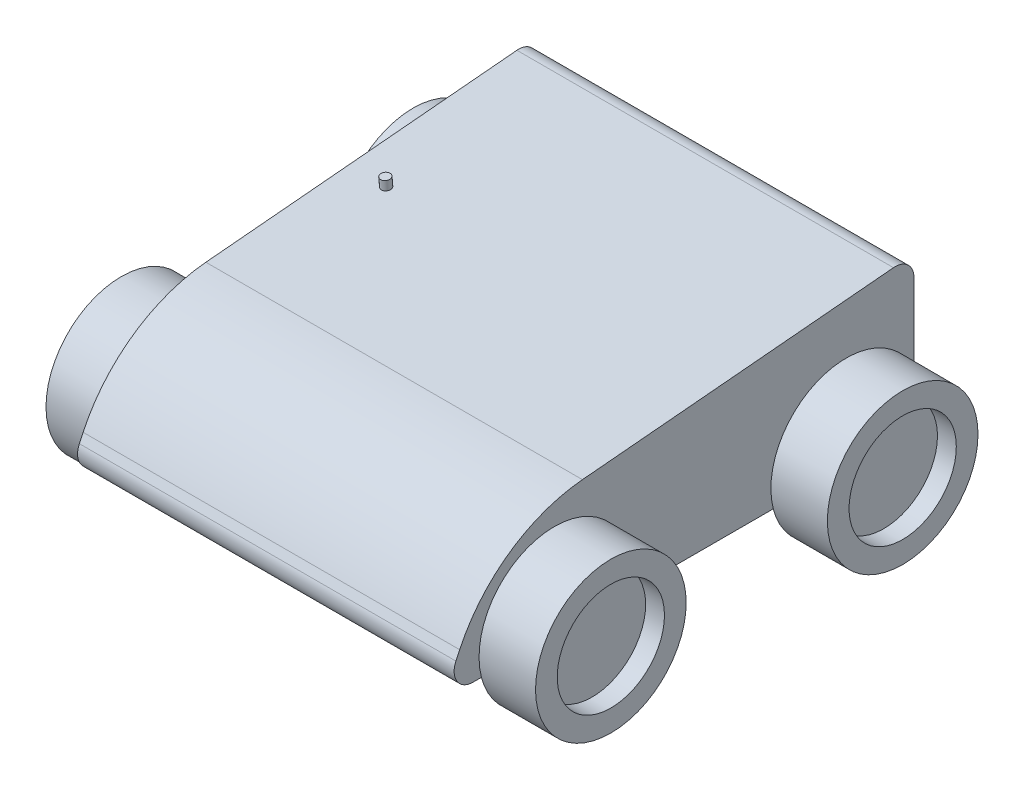
SolidWorks part; units mm, degrees
ref_plane "Front Plane" through (0, 0, 0) normal (0, 0, 1) x (1, 0, 0)
ref_plane "Top Plane" through (0, 0, 0) normal (0, 1, 0) x (1, 0, 0)
ref_plane "Right Plane" through (0, 0, 0) normal (1, 0, 0) x (0, 0, -1)
sketch "Sketch2" plane through (0, 0, 0) normal (1, 0, 0) x (0, 0, -1)
  line L0 (-112.6439, 14.2578) -> (-110.6453, 18.5051)
  line L1 (-45.4449, 64.1191) -> (119.7486, 79.0171)
  line L2 (130.6468, 69.0576) -> (130.6468, 10)
  line L3 (120.6468, 0) -> (-103.5956, 0)
  arc A0 (-110.6453, 18.5051) -> (-45.4449, 64.1191) centre (-38.2592, -15.5575) cw
  arc A1 (-112.6439, 14.2578) -> (-103.5956, 0) centre (-103.5956, 10) ccw
  arc A2 (130.6468, 10) -> (120.6468, 0) centre (120.6468, 10) cw
  arc A3 (119.7486, 79.0171) -> (130.6468, 69.0576) centre (120.6468, 69.0576) cw
  point P6 (-91.1191, 60)
  point P9 (-119.3532, 0)
  point P12 (130.6468, 0)
  point P15 (130.6468, 80)
  dimension "D4" = 80
  dimension "D5" = 10
  dimension "D6" = 10
  dimension "D1" = 250
  dimension "D2" = 80
  dimension "D3" = 60
extrude "Boss-Extrude1" add sketch "Sketch2" along normal mid plane 200
sketch "Sketch3" plane through (100, 0, 0) normal (1, 0, 0) x (0, 0, -1)
  line L0 (-103.5956, 0) -> (120.6468, 0) construction
  circle A0 centre (-60.3575, 10) radius 25
  circle A1 centre (95.5617, 10) radius 25
  dimension "D1" = 50
  dimension "D2" = 10
  dimension "D3" = 10
extrude "Cut-Extrude1" cut sketch "Sketch3" against normal blind 50
mirror "Mirror1" about plane through (0, 0, 0) normal (1, 0, 0) of "Cut-Extrude1"
sketch "Sketch4" plane through (0, 67.6672, 6.1026) normal (0, 0.996, 0.0898) x (1, 0, 0)
  line L0 (-100, 126.362) -> (-100, -39.502) construction
  circle A0 centre (-80, 36.5744) radius 2.5
  dimension "D1" = 5
  dimension "D2" = 20
extrude "Boss-Extrude2" add sketch "Sketch4" along normal blind 5
sketch "Sketch5" plane through (100, 0, 0) normal (1, 0, 0) x (0, 0, -1)
  circle A0 centre (-60.3575, 10) radius 40
  dimension "D1" = 80
extrude "Boss-Extrude3" add sketch "Sketch5" along normal blind 30
sketch "Sketch6" plane through (130, 0, 0) normal (1, 0, 0) x (0, 0, -1)
  circle A0 centre (-60.3575, 10) radius 28.477
extrude "Cut-Extrude2" cut sketch "Sketch6" against normal blind 10
pattern_linear "LPattern1" count 2 spacing 155 along (0, 0, -1) of "Cut-Extrude2", "Boss-Extrude3"
mirror "Mirror2" about plane through (0, 0, 0) normal (1, 0, 0) of "LPattern1"
